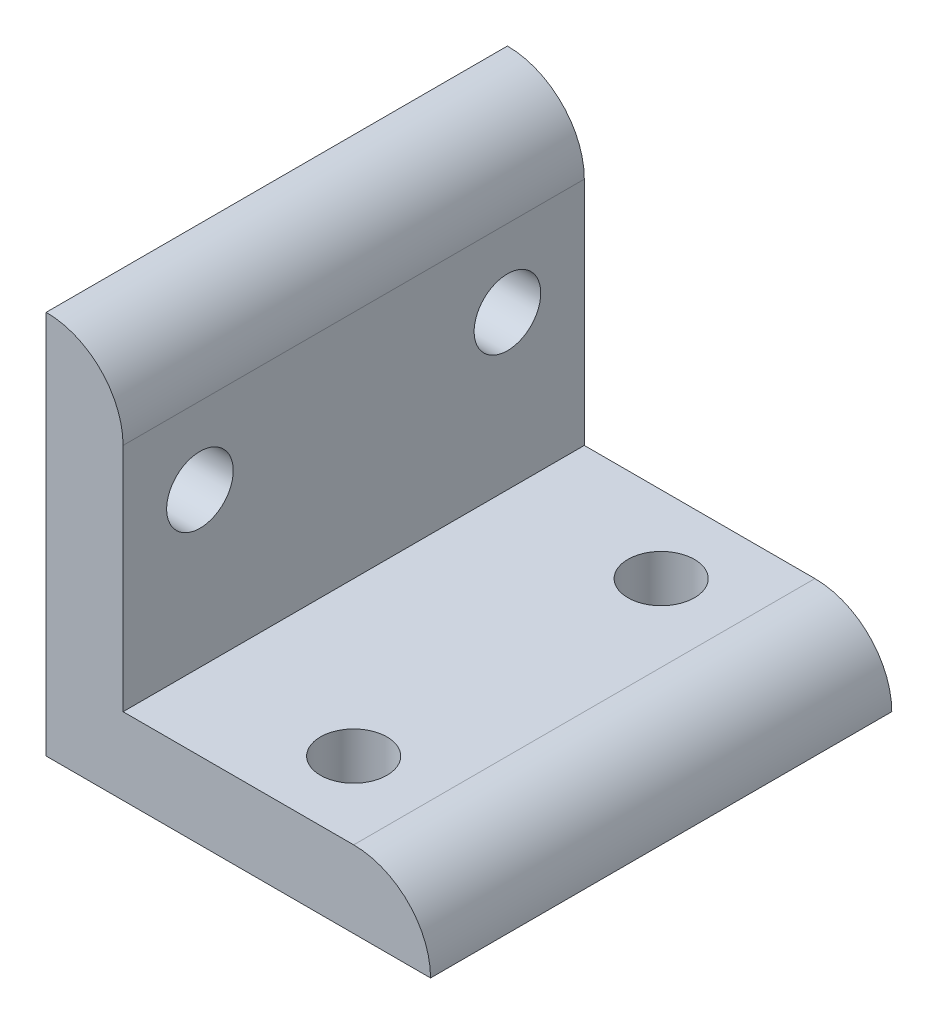
SolidWorks part; units mm, degrees
material "AISI 1045 Steel, cold drawn"
ref_plane "Front Plane" through (0, 0, 0) normal (0, 0, 1) x (1, 0, 0)
ref_plane "Top Plane" through (0, 0, 0) normal (0, 1, 0) x (1, 0, 0)
ref_plane "Right Plane" through (0, 0, 0) normal (1, 0, 0) x (0, 0, -1)
sketch "Sketch1" plane through (0, 0, 0) normal (0, 0, 1) x (1, 0, 0)
  line L0 (0, 0) -> (31.75, 0)
  line L1 (31.75, 0) -> (31.75, 6.35)
  line L2 (31.75, 6.35) -> (6.35, 6.35)
  line L3 (6.35, 6.35) -> (6.35, 31.75)
  line L4 (6.35, 31.75) -> (0, 31.75)
  line L5 (0, 31.75) -> (0, 0)
  dimension "D1" = 31.75
  dimension "D2" = 6.35
extrude "Boss-Extrude1" add sketch "Sketch1" along normal blind 38.1
fillet "Fillet1" radius 6.35 2 edges at (31.75, 6.35, 19.05) (6.35, 31.75, 19.05)
hole_wizard "M5 Clearance Hole1" positions "Sketch2" profile "Sketch3" hole size "M5" standard "ANSI Metric" end condition up to next
sketch "Sketch2" plane through (6.35, 0, 0) normal (1, 0, 0) x (0, 0, -1)
  line L0 (-31.75, 19.05) -> (-6.35, 19.05) construction
  line L2 (-38.1, 31.75) -> (0, 31.75) construction
  line L3 (-38.1, 0) -> (0, 0) construction
  point P0 (-31.75, 19.05)
  point P2 (-6.35, 19.05)
  point P11 (-19.05, 31.75)
  point P12 (-19.05, 19.05)
  dimension "D1" = 25.4
  dimension "D2" = 19.05
sketch "Sketch3" plane through (6.35, 19.05, 31.75) normal (0, 1, 0) x (0, 0, -1)
  line L0 (0, 0) -> (0, 6.35)
  line L1 (0, 6.35) -> (2.75, 6.35)
  line L2 (2.75, 6.35) -> (2.75, 0)
  line L5 (2.75, 0) -> (0, 0)
  line L11 (0, -6.35) -> (0, 107.95) construction
  dimension "Thru Hole Dia." = 5.5
  dimension "Thru Hole Depth" = 6.35
ref_plane "Plane1" through (0, 0, 0) normal (-0.7071, 0.7071, 0) x (0.7071, 0.7071, 0)
mirror "Mirror1" about plane through (0, 0, 0) normal (-0.7071, 0.7071, 0) of "M5 Clearance Hole1"
